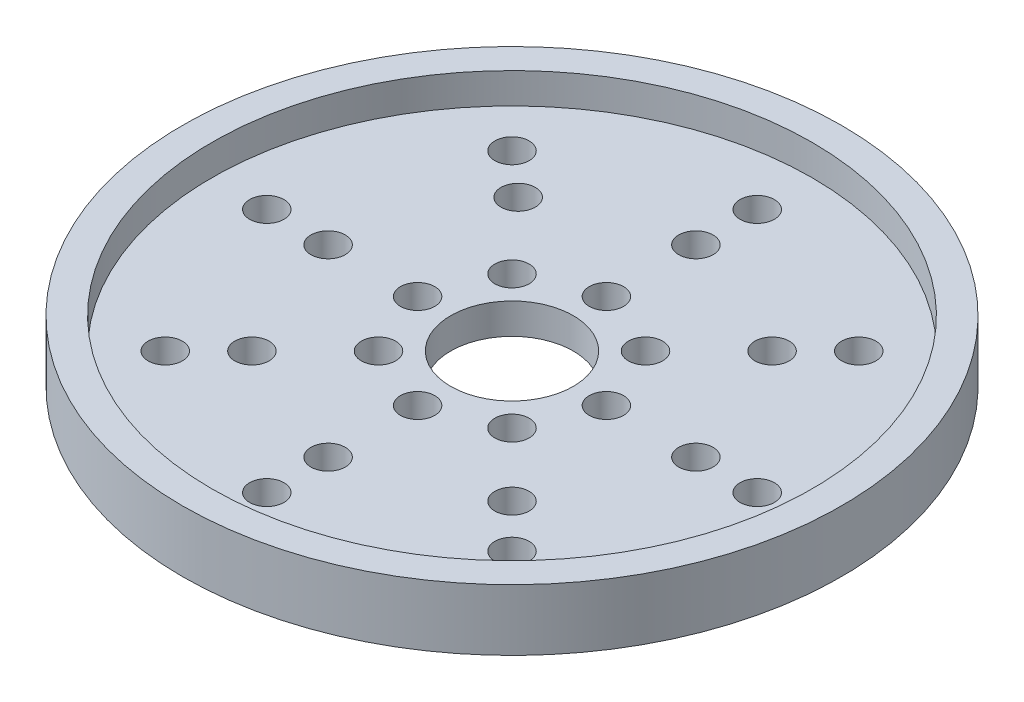
SolidWorks part; units mm, degrees
material "6061-T6 (SS)"
ref_plane "Front Plane" through (0, 0, 0) normal (0, 0, 1) x (1, 0, 0)
ref_plane "Top Plane" through (0, 0, 0) normal (0, 1, 0) x (1, 0, 0)
ref_plane "Right Plane" through (0, 0, 0) normal (1, 0, 0) x (0, 0, -1)
sketch "Sketch1" plane through (0, 0, 0) normal (0, 1, 0) x (1, 0, 0)
  circle A0 centre (0, 0) radius 34.1376
  dimension "D1" = 68.2752
extrude "Boss-Extrude1" add sketch "Sketch1" along normal blind 6.35
sketch "Sketch2" plane through (0, 6.35, 0) normal (0, 1, 0) x (1, 0, 0)
  circle A0 centre (0, 0) radius 31.0896
  circle A1 centre (0, 0) radius 34.1376 construction
  dimension "D1" = 3.048
extrude "Cut-Extrude3" cut sketch "Sketch2" against normal blind 3.175
sketch "Sketch3" plane through (0, 3.175, 0) normal (0, 1, 0) x (1, 0, 0)
  line L0 (0, 0) -> (0, 25.4) construction
  line L1 (0, 0) -> (0, -25.4) construction
  line L2 (0, 0) -> (25.4, 0) construction
  line L3 (0, 0) -> (-25.4, 0) construction
  line L4 (0, 0) -> (17.9605, 17.9605) construction
  line L5 (0, 0) -> (-17.9605, 17.9605) construction
  line L6 (0, 0) -> (-17.9605, -17.9605) construction
  line L7 (0, 0) -> (17.9605, -17.9605) construction
  circle A0 centre (0, 0) radius 6.35
  circle A1 centre (25.4, 0) radius 1.778
  circle A2 centre (17.9605, 17.9605) radius 1.778
  circle A3 centre (0, 25.4) radius 1.778
  circle A4 centre (-17.9605, 17.9605) radius 1.778
  circle A5 centre (-25.4, 0) radius 1.778
  circle A6 centre (-17.9605, -17.9605) radius 1.778
  circle A7 centre (0, -25.4) radius 1.778
  circle A8 centre (17.9605, -17.9605) radius 1.778
  dimension "D1" = 12.7
  dimension "D2" = 3.556
  dimension "D3" = 25.4
  dimension "D4" = 35.921
  dimension "D5" = 35.921
extrude "Cut-Extrude4" cut sketch "Sketch3" against normal blind 3.175 contours A0
extrude "Cut-Extrude5" cut sketch "Sketch3<3>" against normal blind 3.175
sketch "Sketch3<3>" plane through (0, 3.175, 0) normal (0, 1, 0) x (1, 0, 0) same geometry as "Sketch3"
sketch "Sketch6" plane through (0, 3.175, 0) normal (0, 1, 0) x (1, 0, 0)
  line L0 (0, 0) -> (0, 19.05) construction
  line L1 (0, 0) -> (19.05, 0) construction
  line L2 (0, 0) -> (-19.05, 0) construction
  line L3 (0, 0) -> (0, -19.05) construction
  line L4 (0, 0) -> (13.4704, 13.4704) construction
  line L5 (0, 0) -> (-13.4704, -13.4704) construction
  line L6 (0, 0.6386) -> (-13.4704, 14.109) construction
  line L7 (0, 0) -> (13.4704, -13.4704) construction
  circle A0 centre (0, 19.05) radius 1.778
  circle A1 centre (-13.4704, 14.109) radius 1.778
  circle A2 centre (-19.05, 0) radius 1.778
  circle A3 centre (-13.4704, -13.4704) radius 1.778
  circle A4 centre (0, -19.05) radius 1.778
  circle A5 centre (13.4704, -13.4704) radius 1.778
  circle A6 centre (19.05, 0) radius 1.778
  circle A7 centre (13.4704, 13.4704) radius 1.778
  dimension "D1" = 3.556
  dimension "D2" = 19.05
  dimension "D3" = 14.5802
  dimension "D4" = 14.348
extrude "Cut-Extrude6" cut sketch "Sketch6" against normal blind 3.175
sketch "Sketch8" plane through (0, 3.175, 0) normal (0, 1, 0) x (1, 0, 0)
  line L0 (0, 0) -> (9.779, 0) construction
  line L1 (0, 0) -> (-9.779, 0) construction
  line L2 (0, 0) -> (0, 9.779) construction
  line L3 (0, 0) -> (0, -9.779) construction
  line L4 (0, 0) -> (6.9148, 6.9148) construction
  line L5 (0, 0) -> (-6.9148, 6.9148) construction
  line L6 (0, 0) -> (-6.9148, -6.9148) construction
  line L7 (0, 0) -> (6.9148, -6.9148) construction
  circle A0 centre (9.779, 0) radius 1.778
  circle A1 centre (6.9148, 6.9148) radius 1.778
  circle A2 centre (0, 9.779) radius 1.778
  circle A3 centre (-6.9148, 6.9148) radius 1.778
  circle A4 centre (-9.779, 0) radius 1.778
  circle A5 centre (-6.9148, -6.9148) radius 1.778
  circle A6 centre (0, -9.779) radius 1.778
  circle A7 centre (6.9148, -6.9148) radius 1.778
  dimension "D1" = 3.556
  dimension "D2" = 9.779
  dimension "D3" = 7.4845
extrude "Cut-Extrude7" cut sketch "Sketch8" against normal blind 3.175
